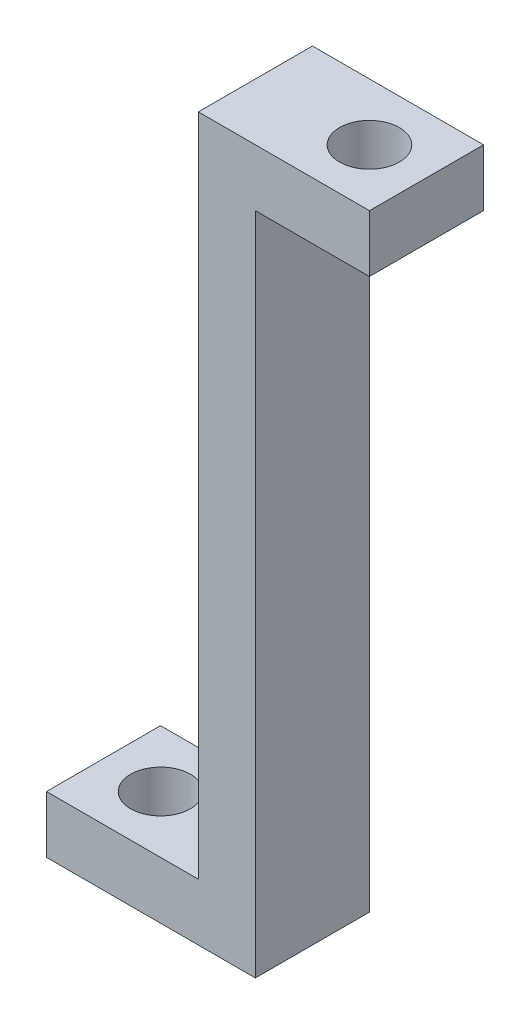
SolidWorks part; units mm, degrees
ref_plane "Front Plane" through (0, 0, 0) normal (0, 0, 1) x (1, 0, 0)
ref_plane "Top Plane" through (0, 0, 0) normal (0, 1, 0) x (1, 0, 0)
ref_plane "Right Plane" through (0, 0, 0) normal (1, 0, 0) x (0, 0, -1)
sketch "Sketch1" plane through (0, 0, 0) normal (0, 1, 0) x (1, 0, 0)
  line L0 (0, 0) -> (-2, 0) construction
  line L1 (-2, 2) -> (3.325, 2)
  line L2 (-2, 2) -> (-2, -2)
  line L3 (-2, -2) -> (3.325, -2)
  line L4 (3.325, 2) -> (3.325, -2)
  line L5 (0, 0) -> (0, -2) construction
  circle A0 centre (0, 0) radius 1.05
  point P0 (0, 0)
  dimension "D3" = 2.1
  dimension "D1" = 12
  dimension "D2" = 4
  dimension "D4" = 2
extrude "Boss-Extrude1" add sketch "Sketch1" along normal blind 2
sketch "Sketch2" plane through (0, 0, 0) normal (0, 1, 0) x (1, 0, 0)
  line L0 (3.325, -2) -> (5.325, -2)
  line L2 (5.325, -2) -> (5.325, 2)
  line L3 (5.325, 2) -> (3.325, 2)
  line L4 (3.325, -2) -> (3.325, 2) construction
  line L5 (3.325, 2) -> (3.325, -2)
  dimension "D1" = 2
extrude "Boss-Extrude2" add sketch "Sketch2" along normal up to surface (25.3 mm away) up to face at (0.6625, 0, 0)
sketch "Sketch3" plane through (0, 25.3, 0) normal (0, 1, 0) x (1, 0, 0)
  line L8 (5.325, 2) -> (9.325, 2)
  line L9 (9.325, 2) -> (9.325, -2)
  line L10 (9.325, -2) -> (5.325, -2)
  line L11 (5.325, 2) -> (5.325, -2)
  line L13 (7.325, 0) -> (9.325, 0) construction
  line L14 (7.325, 0) -> (7.325, 2) construction
  circle A2 centre (7.325, 0) radius 1.05
  dimension "D2" = 2.1
  dimension "D1" = 4
extrude "Boss-Extrude3" add sketch "Sketch3" against normal blind 2
